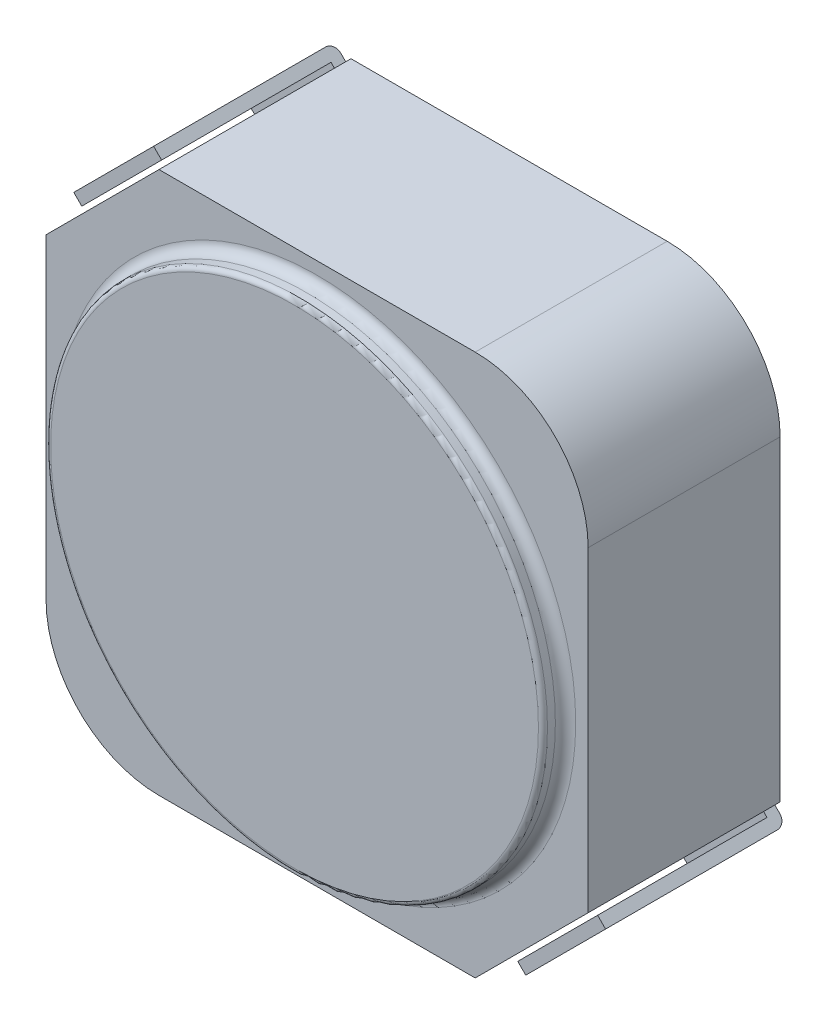
SolidWorks part; units mm, degrees
ref_plane "Спереди" through (0, 0, 0) normal (0, 0, 1) x (1, 0, 0)
ref_plane "Сверху" through (0, 0, 0) normal (0, 1, 0) x (1, 0, 0)
ref_plane "Справа" through (0, 0, 0) normal (1, 0, 0) x (0, 0, -1)
sketch "Эскиз2" plane through (0, 0, 0) normal (0, 0, 1) x (1, 0, 0)
  line L1 (-1.4, 2.4) -> (1.4, 2.4)
  line L2 (-2.4, 1.4) -> (-2.4, -1.4)
  line L3 (-1.4, -2.4) -> (1.4, -2.4)
  line L4 (2.4, 1.4) -> (2.4, -1.4)
  line L5 (-2.4, -2.4) -> (2.4, -2.4) construction
  line L6 (-2.4, 1.4) -> (-1.4, 2.4)
  line L7 (-2.4, -2.4) -> (-2.4, 2.4) construction
  line L8 (-2.4, 2.4) -> (2.4, 2.4) construction
  line L9 (1.4, -2.4) -> (2.4, -1.4)
  line L10 (2.4, -2.4) -> (2.4, 2.4) construction
  line L11 (-2.4, -2.4) -> (2.4, 2.4) construction
  line L12 (-2.4, 2.4) -> (2.4, -2.4) construction
  arc A0 (-2.4, -1.4) -> (-1.4, -2.4) centre (-1.4, -1.4) ccw
  arc A1 (2.4, 1.4) -> (1.4, 2.4) centre (1.4, 1.4) ccw
  point P0 (-2.4, 2.4)
  point P1 (2.4, -2.4)
  point P8 (0, 0)
  dimension "D1" = 1
  dimension "D2" = 1
  dimension "D4" = 4.8
extrude "Вытянуть1" add sketch "Эскиз2" along normal blind 1.7 from offset 0.1
sketch "Эскиз6" plane through (0, 0, 0) normal (0, 0, 1) x (1, 0, 0)
  circle A1 centre (0, 0) radius 2
extrude "Вытянуть5" cut sketch "Эскиз6" along normal blind 0.3
sketch "Эскиз8" plane through (0, 0, 0) normal (0, 0, 1) x (1, 0, 0)
  circle A0 centre (0, 0) radius 1.7
extrude "Вытянуть9" add sketch "Эскиз8" along normal blind 0.25 from offset 0.1
sketch "Эскиз9" plane through (0, 0, 1.8) normal (0, 0, 1) x (1, 0, 0)
  circle A0 centre (0, 0) radius 2.2
  dimension "D1" = 4.4
extrude "Бобышка-Вытянуть1" add sketch "Эскиз9" along normal blind 0.2
fillet "Скругление2" radius 0.09 1 edges at (2.2, 0, 1.8)
fillet "Скругление3" radius 0.04 1 edges at (2.2, 0, 2)
sketch "Эскиз10" plane through (0, 0, 0) normal (0, 0, 1) x (1, 0, 0)
  line L0 (2.25, 0.75) -> (1.5, 0.75)
  line L1 (-2.25, 0.75) -> (-1.5, 0.75)
  line L2 (1.5, 2.25) -> (-1.55, 2.25)
  line L3 (2.25, 0.75) -> (2.25, 1.5)
  line L4 (-2.25, 0.75) -> (-2.25, 1.55)
  line L5 (1.5, 2.25) -> (2.25, 1.5)
  line L6 (-1.55, 2.25) -> (-2.25, 1.55)
  line L7 (-2.25, -0.75) -> (-1.5, -0.75)
  line L8 (2.25, -0.75) -> (1.5, -0.75)
  line L9 (-1.5, -2.25) -> (1.55, -2.25)
  line L10 (-2.25, -0.75) -> (-2.25, -1.5)
  line L11 (2.25, -0.75) -> (2.25, -1.55)
  line L12 (-1.5, -2.25) -> (-2.25, -1.5)
  line L13 (1.55, -2.25) -> (2.25, -1.55)
  arc A0 (1.5, 0.75) -> (-1.5, 0.75) centre (0, 0) ccw
  arc A1 (-1.5, -0.75) -> (1.5, -0.75) centre (0, 0) ccw
  dimension "D1" = 2
extrude "Бобышка-Вытянуть2" add sketch "Эскиз10" along normal blind 0.1
ref_axis "Ось1" through (0, 0, -0.15) along (0, 0, 1)
ref_plane "Плоскость2" through (0, 0, 0) normal (-0.7071, 0.7071, 0) x (-0.7071, -0.7071, 0)
sketch "Эскиз11" plane through (0, 0, 0) normal (0.7071, -0.7071, 0) x (0, 0, -1)
  line L0 (-0.1, 0.5303) -> (-0.1, 0.5484) construction
  line L1 (-1.6, 0.5) -> (-0.1, 0.5)
  line L2 (-1.6, 0.5) -> (-1.6, -0.5)
  line L3 (-1.6, -0.5) -> (-0.1, -0.5)
  line L4 (-0.1, 0.5) -> (-0.1, -0.5)
  line L5 (0, 0) -> (-1.6, 0) construction
  line L6 (-1.6, 0) -> (-1.8, 0) construction
  line L7 (-1.8, 2.29) -> (-1.8, -2.29) construction
  point P9 (-0.1, 0)
  point P10 (0, 0)
  dimension "D1" = 1
  dimension "D2" = 0.2
extrude "Бобышка-Вытянуть3" add sketch "Эскиз11" along normal blind 0.1 from offset 2.73 separate body
extrude "Бобышка-Вытянуть4" add sketch "Эскиз11<2>" against normal blind 0.1 from offset 2.73 separate body offset against normal yes
sketch "Эскиз11<2>" plane through (0, 0, 0) normal (0.7071, -0.7071, 0) x (0, 0, -1) same geometry as "Эскиз11"
ref_plane "Плоскость3" through (0, 0, 0) normal (-0.7071, -0.7071, 0) x (0.7071, -0.7071, 0)
sketch "Эскиз12" plane through (0, 0, 0) normal (-0.7071, -0.7071, 0) x (0.7071, -0.7071, 0)
  line L0 (2.83, 0.15) -> (2.83, 0.08)
  line L1 (2.75, 0) -> (2.6, 0)
  line L2 (2.6, 0.1) -> (2.73, 0.1)
  line L3 (2.73, 0.1) -> (2.73, 0.15)
  line L4 (2.73, 0.15) -> (2.83, 0.15)
  line L5 (2.6, 0.1) -> (2.6, 0)
  line L6 (0, -0.6039) -> (0, -0.4596) construction
  line L7 (-2.6, 0.1) -> (-2.6, 0)
  line L8 (-2.73, 0.15) -> (-2.83, 0.15)
  line L9 (-2.73, 0.1) -> (-2.73, 0.15)
  line L10 (-2.6, 0.1) -> (-2.73, 0.1)
  line L11 (-2.75, 0) -> (-2.6, 0)
  line L12 (-2.83, 0.15) -> (-2.83, 0.08)
  arc A0 (2.83, 0.08) -> (2.75, 0) centre (2.75, 0.08) cw
  arc A1 (-2.83, 0.08) -> (-2.75, 0) centre (-2.75, 0.08) ccw
  dimension "D1" = 0.08
extrude "Бобышка-Вытянуть5" add sketch "Эскиз12" against normal blind 1 from offset 0.5
